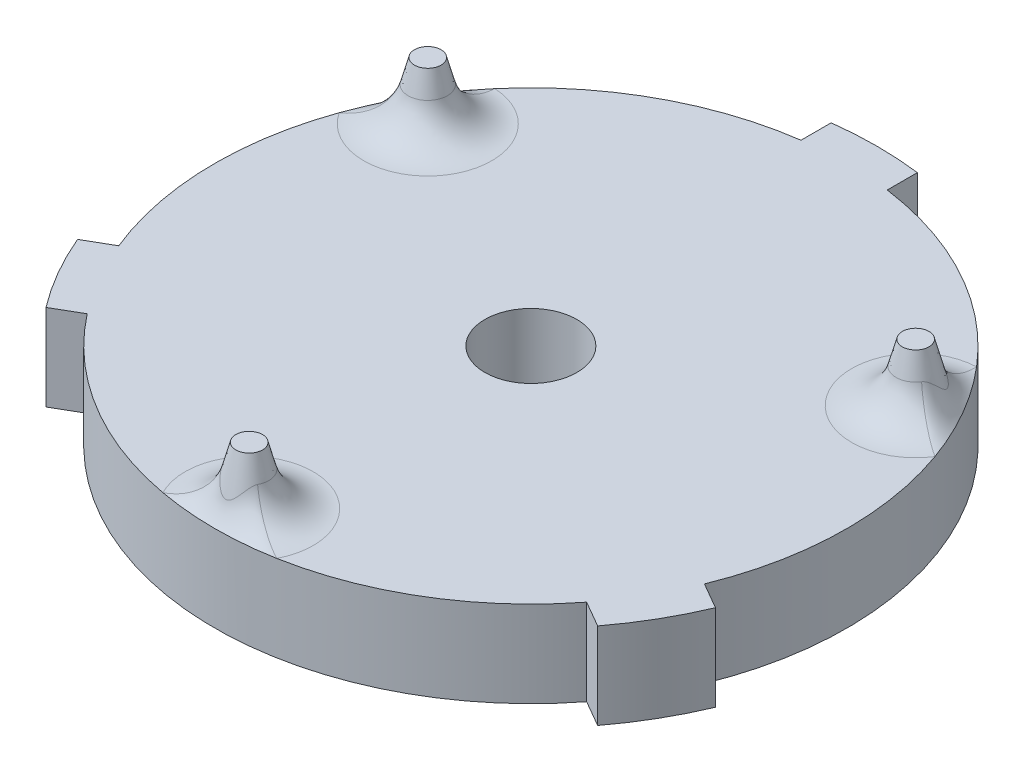
SolidWorks part; units mm, degrees
ref_plane "Front Plane" through (0, 0, 0) normal (0, 0, 1) x (1, 0, 0)
ref_plane "Top Plane" through (0, 0, 0) normal (0, 1, 0) x (1, 0, 0)
ref_plane "Right Plane" through (0, 0, 0) normal (1, 0, 0) x (0, 0, -1)
sketch "Sketch1" plane through (0, 0, 0) normal (0, 1, 0) x (1, 0, 0)
  line L0 (-4.7625, 34.5988) -> (-4.7625, 37.9292)
  line L2 (4.7625, 37.9292) -> (4.7625, 34.5988)
  line L3 (32.3447, -13.1749) -> (35.2289, -14.8401)
  line L5 (30.4664, -23.089) -> (27.5822, -21.4238)
  line L6 (-27.5822, -21.4238) -> (-30.4664, -23.089)
  line L8 (-35.2289, -14.8401) -> (-32.3447, -13.1749)
  arc A0 (-35.2289, -14.8401) -> (-30.4664, -23.089) centre (0, 0) ccw
  arc A1 (-27.5822, -21.4238) -> (27.5822, -21.4238) centre (0, 0) ccw
  arc A2 (4.7625, 37.9292) -> (-4.7625, 37.9292) centre (0, 0) ccw
  arc A3 (30.4664, -23.089) -> (35.2289, -14.8401) centre (0, 0) ccw
  arc A4 (-4.7625, 34.5988) -> (-32.3447, -13.1749) centre (0, 0) ccw
  arc A5 (32.3447, -13.1749) -> (4.7625, 34.5988) centre (0, 0) ccw
  point P19 (0, 0)
  dimension "D1" = 76.454
  dimension "D4" = 69.85
  dimension "D2" = 9.525
  dimension "D3" = 3
extrude "Boss-Extrude1" add sketch "Sketch1" along normal blind 9.525
sketch "Sketch2" plane through (0, 9.525, 0) normal (0, 1, 0) x (1, 0, 0)
  line L0 (0, 0) -> (0, 53.0634) construction
  line L1 (0, 0) -> (-53.8689, 31.1012) construction
  circle A0 centre (0, 0) radius 38.354 construction
  circle A1 centre (0, 0) radius 27.178 construction
  circle A2 centre (-26.9464, 15.5575) radius 3.175
  circle A3 centre (26.9464, 15.5575) radius 3.175
  circle A4 centre (0, -31.115) radius 3.175
  point P14 (0, 0)
  dimension "D1" = 54.356
  dimension "D2" = 76.708
  dimension "D4" = 6.35
  dimension "D3" = 60
  dimension "D5" = 31.115
  dimension "D6" = 3
extrude "Boss-Extrude2" add sketch "Sketch2" along normal blind 6.35 draft 15
fillet "Fillet1" radius 5.08 3 edges at (26.9464, 9.525, -12.3825) (0, 9.525, 34.29) (-26.9464, 9.525, -12.3825)
sketch "Sketch3" plane through (0, 9.525, 0) normal (0, 1, 0) x (1, 0, 0)
  circle A0 centre (0, 0) radius 5.08
  dimension "D1" = 10.16
extrude "Cut-Extrude1" cut sketch "Sketch3" against normal through all
